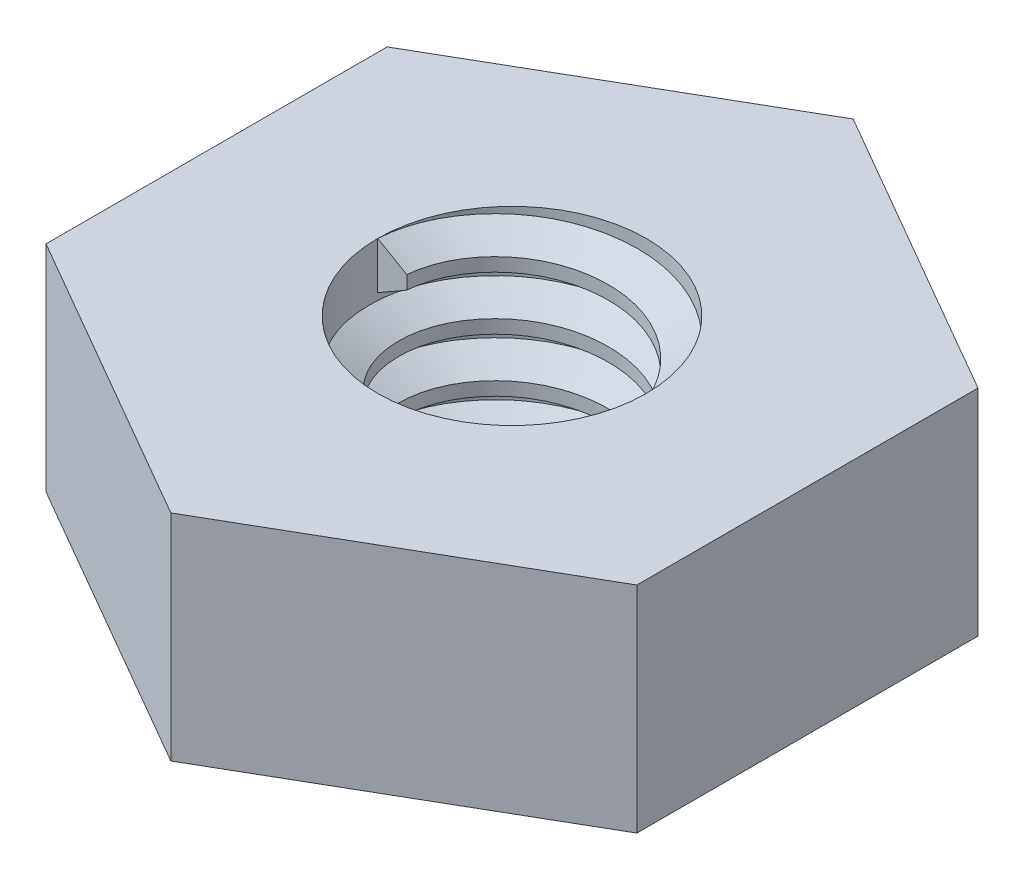
SolidWorks part; units mm, degrees
material "1.4310 (X10CrNi18-8)"
ref_plane "Front Plane" through (0, 0, 0) normal (0, 0, 1) x (1, 0, 0)
ref_plane "Top Plane" through (0, 0, 0) normal (0, 1, 0) x (1, 0, 0)
ref_plane "Right Plane" through (0, 0, 0) normal (1, 0, 0) x (0, 0, -1)
sketch "Sketch1" plane through (0, 0, 0) normal (0, 1, 0) x (1, 0, 0)
  line L1 (0, 5.041) -> (-4.3656, 2.5205)
  line L2 (-4.3656, 2.5205) -> (-4.3656, -2.5205)
  line L3 (-4.3656, -2.5205) -> (0, -5.041)
  line L4 (0, -5.041) -> (4.3656, -2.5205)
  line L5 (4.3656, -2.5205) -> (4.3656, 2.5205)
  line L6 (4.3656, 2.5205) -> (0, 5.041)
  circle A0 centre (0, 0) radius 1.9844
  circle A1 centre (0, 0) radius 4.3656 construction
  dimension "D1" = 3.9688
  dimension "D2" = 8.7312
extrude "Boss-Extrude1" add sketch "Sketch1" along normal blind 3.175
thread "Thread1" pitch 0.7937 method extrude profile "Thread Profile1" start angle 0, offset 0, length 0, pitch 0.7937, diameter 3.9688
ref_plane "Plane1" through (-1.9844, 3.175, 0) normal (0, 0, 1) x (-1, 0, 0)
sketch "Thread Profile1" plane through (-1.9844, 3.175, 0) normal (0, 0, 1) x (-1, 0, 0)
  line L0 (0, 0) -> (0, 0.7937) construction
  line L11 (0, 0) -> (0, 0.6945)
  line L12 (0, 0.6945) -> (-0.4296, 0.4465)
  line L13 (-0.4296, 0.4465) -> (-0.4296, 0.248)
  line L15 (-0.4296, 0.248) -> (0, 0)
  line L17 (-0.4296, 0.3473) -> (0, 0.3473) construction
  point P2 (0, 0)
  dimension "Pitch" = 0.7937
  dimension "Profile_Angle" = 60
  dimension "Profile_Land" = 0.1984
  dimension "Profile_Height" = 0.4296
